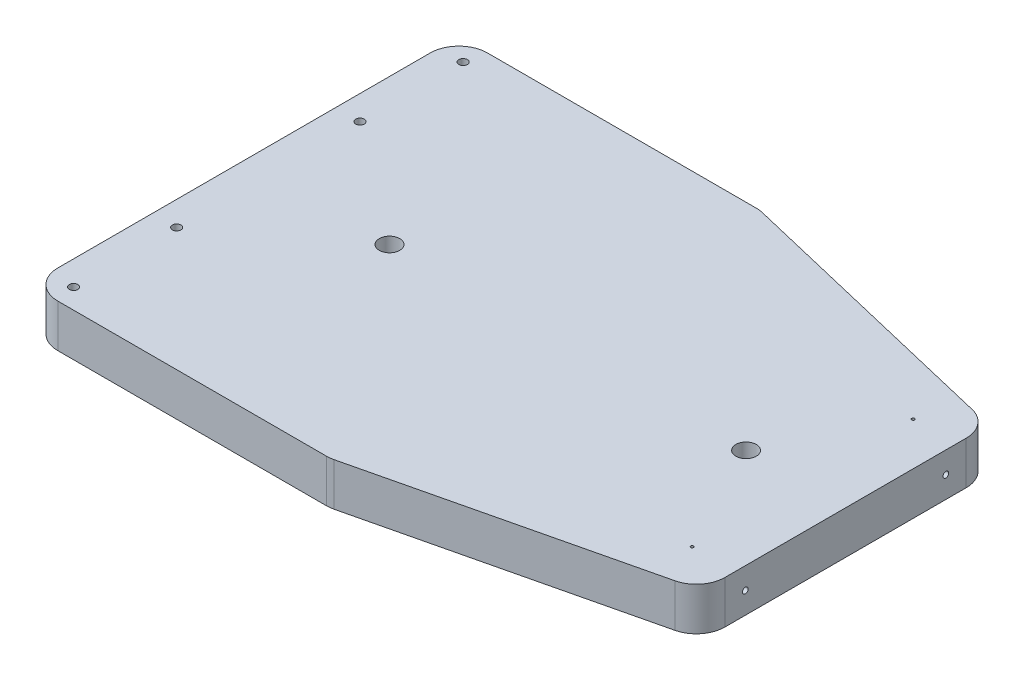
SolidWorks part; units mm, degrees
material "Carvalho"
ref_plane "Plano frontal" through (0, 0, 0) normal (0, 0, 1) x (1, 0, 0)
ref_plane "Plano superior" through (0, 0, 0) normal (0, 1, 0) x (1, 0, 0)
ref_plane "Plano direito" through (0, 0, 0) normal (1, 0, 0) x (0, 0, -1)
sketch "Esboço1" plane through (0, 0, 0) normal (0, 1, 0) x (1, 0, 0)
  line L0 (210, 50) -> (105, 75)
  line L1 (0, -75) -> (105, -75)
  line L2 (0, -75) -> (0, 75)
  line L3 (0, 75) -> (105, 75)
  line L4 (210, -50) -> (210, 50)
  line L5 (195, -38.5714) -> (210, -38.5714) construction
  line L6 (195, -38.5714) -> (195, -53.5714) construction
  line L7 (105, -75) -> (210, -50)
  line L8 (-14.8259, 0) -> (14.392, 0) construction
  line L9 (0, 21.2472) -> (0, -16.7598) construction
  circle A0 centre (50.8, 0) radius 3.5719
  circle A1 centre (175.26, 0) radius 3.57
  circle A2 centre (8.5, -68) radius 1.5
  circle A3 centre (8.5, -32) radius 1.5
  circle A4 centre (8.5, 32) radius 1.5
  circle A5 centre (8.5, 68) radius 1.5
  circle A6 centre (195, -38.5714) radius 0.5
  circle A7 centre (195, 38.5714) radius 0.5
  point P0 (0, 0)
  dimension "D3" = 7.1437
  dimension "D5" = 7.14
  dimension "D9" = 1
  dimension "D1" = 25
  dimension "D2" = 150
  dimension "D4" = 50.8
  dimension "D6" = 210
  dimension "D7" = 175.26
  dimension "D8" = 105
  dimension "D10" = 15
  dimension "D11" = 15
extrude "Ressalto-extrusão1" add sketch "Esboço1" along normal blind 15
sketch "Esboço2" plane through (210, 0, 0) normal (1, 0, 0) x (0, 0, -1)
  line L0 (0, 0) -> (0, 15) construction
  line L1 (-50, 0) -> (50, 0) construction
  line L2 (-50, 15) -> (50, 15) construction
  circle A0 centre (-35, 7.5) radius 1
  circle A1 centre (35, 7.5) radius 1
  point P8 (0, 7.5)
  dimension "D2" = 2
  dimension "D1" = 35
extrude "Corte-extrusão1" cut sketch "Esboço2" against normal blind 10
fillet "Filete1" radius 10 6 edges at (0, 7.5, 75) (105, 7.5, 75) (210, 7.5, 50) (210, 7.5, -50) (0, 7.5, -75) (105, 7.5, -75)
